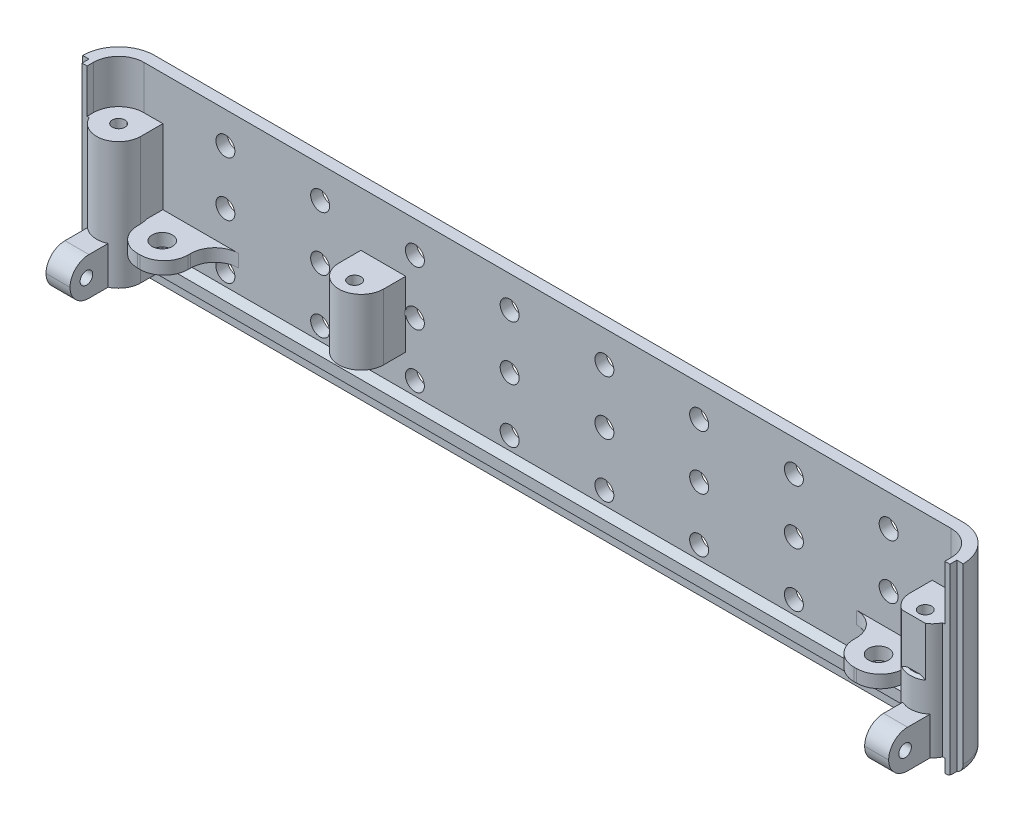
SolidWorks part; units mm, degrees
ref_plane "Спереди" through (0, 0, 0) normal (0, 0, 1) x (1, 0, 0)
ref_plane "Сверху" through (0, 0, 0) normal (0, 1, 0) x (1, 0, 0)
ref_plane "Справа" through (0, 0, 0) normal (1, 0, 0) x (0, 0, -1)
sketch "Эскиз1" plane through (0, 0, 0) normal (0, 0, 1) x (1, 0, 0)
  line L0 (63.5, -15.75) -> (-63.5, -15.75)
  line L1 (63.5, -15.75) -> (67.5, -15.75)
  line L2 (-67.5, -15.75) -> (-63.5, -15.75)
  line L3 (46.9932, -6.75) -> (37.9073, -6.75)
  line L4 (37.9073, -5.75) -> (46.9932, -5.75)
  line L5 (47.9512, -6.625) -> (47.9512, -6.1632)
  line L6 (47.912, -5.875) -> (47.023, -5.875)
  line L7 (47.023, -5.875) -> (47.023, -6.625)
  line L8 (47.023, -6.625) -> (47.9512, -6.625)
  line L9 (36.95, -6.1597) -> (36.95, -6.625)
  line L10 (36.95, -6.625) -> (37.8781, -6.625)
  line L11 (37.8781, -6.625) -> (37.8781, -5.875)
  line L12 (37.8781, -5.875) -> (36.9862, -5.875)
  line L13 (67.5, -13.75) -> (67.5, -15.75)
  line L14 (-67.5, -13.75) -> (-67.5, -15.75)
  line L15 (63.5, -13.75) -> (-63.5, -13.75)
  line L16 (57.5, -7.55) -> (-57.5, -7.55)
  line L17 (-60, -7.55) -> (-60, -9.15)
  line L18 (60, -9.15) -> (60, -7.55)
  line L19 (37.2238, 0.43) -> (27.8238, 0.43)
  line L20 (37.2238, -0.52) -> (27.8238, -0.52)
  line L21 (27.0238, -0.52) -> (27.0238, 0.43)
  line L22 (38.0238, 0.43) -> (38.0238, -0.52)
  line L23 (38.325, 15.75) -> (32.995, 15.75)
  line L24 (43.655, 15.75) -> (38.325, 15.75)
  line L25 (67.5, -13.75) -> (63.5, -13.75)
  line L26 (-63.5, -13.75) -> (-67.5, -13.75)
  line L27 (-26.445, 5.4154) -> (64.8363, 5.4154)
  line L28 (-26.445, 7.0154) -> (64.8363, 7.0154)
  line L29 (63.0185, 5.4154) -> (66.0185, 5.4154)
  line L30 (-24.6275, 7.05) -> (-27.6275, 7.05)
  arc A0 (-11.5687, 1.25) -> (-15.0687, 1.25) centre (-13.3187, 1.25) ccw
  arc A1 (-15.0687, 1.25) -> (-11.5687, 1.25) centre (-13.3187, 1.25) ccw
  arc A2 (53.36, 1.25) -> (49.86, 1.25) centre (51.61, 1.25) ccw
  arc A3 (49.86, 1.25) -> (53.36, 1.25) centre (51.61, 1.25) ccw
  arc A4 (17.6413, 1.25) -> (14.1413, 1.25) centre (15.8913, 1.25) ccw
  arc A5 (14.1413, 1.25) -> (17.6413, 1.25) centre (15.8913, 1.25) ccw
  arc A6 (-1.428, -0.6365) -> (-1.4312, -5.6346) centre (0.0417, -3.1365) ccw
  arc A7 (1.5146, -5.6346) -> (1.5114, -0.6365) centre (0.0417, -3.1365) ccw
  spline S0 degree 3 poles (47.9512, -6.1632) (47.951, -6.1513) (47.9493, -6.1307) (47.9471, -6.1018) knots 0 0 0 0 0.000128 0.000128 0.000128 0.000128 weights 1 1 1 1
  spline S1 degree 3 poles (47.9471, -6.1018) (47.9414, -6.0263) (47.9296, -5.9508) (47.912, -5.875) knots 0 0 0 0 0.000334 0.000334 0.000334 0.000334 weights 1 1 1 1
  spline S2 degree 3 poles (36.953, -6.1018) (36.9512, -6.1281) (36.95, -6.1474) (36.95, -6.1597) knots 0 0 0 0 0.000115 0.000115 0.000115 0.000115 weights 1 1 1 1
  spline S3 degree 3 poles (36.9862, -5.875) (36.9691, -5.9508) (36.958, -6.0264) (36.953, -6.1018) knots 0 0 0 0 0.000335 0.000335 0.000335 0.000335 weights 1 1 1 1
sketch "Эскиз2" plane through (0, 0, 0) normal (0, 0, 1) x (1, 0, 0)
  line L0 (43.655, 15.75) -> (38.325, 15.75) construction
  line L1 (-69.7, 13.75) -> (69.7, 13.75)
  line L2 (-69.7, 13.75) -> (-69.7, -15.35)
  line L3 (-69.7, -15.35) -> (69.7, -15.35)
  line L4 (69.7, 13.75) -> (69.7, -15.35)
  line L5 (63.5, -15.75) -> (-63.5, -15.75) construction
  line L6 (67.5, -13.75) -> (67.5, -15.75) construction
  line L7 (-67.5, -13.75) -> (-67.5, -15.75) construction
  dimension "D1" = 2
  dimension "D2" = 0.4
  dimension "D3" = 2.2
  dimension "D4" = 2.2
extrude "Бобышка-Вытянуть1" add sketch "Эскиз2" along normal blind 1.8
sketch "Эскиз5" plane through (0, 0, 0) normal (0, 0, -1) x (-1, 0, 0)
  line L0 (69.7, -15.35) -> (-69.7, -15.35) construction
  line L1 (69.7, 13.75) -> (67.9, 13.75)
  line L2 (69.7, 13.75) -> (69.7, -15.35)
  line L3 (69.7, -15.35) -> (67.9, -15.35)
  line L4 (67.9, 13.75) -> (67.9, -15.35)
  line L5 (-63.5, -15.75) -> (63.5, -15.75) construction
  line L6 (-69.7, 13.75) -> (-67.9, 13.75)
  line L7 (-69.7, 13.75) -> (-69.7, -15.75)
  line L8 (-69.7, -15.75) -> (-67.9, -15.75)
  line L9 (-67.9, 13.75) -> (-67.9, -15.75)
  dimension "D1" = 1.8
  dimension "D2" = 1.8
extrude "Бобышка-Вытянуть2" add sketch "Эскиз5" along normal blind 5
fillet "Скругление1" radius 4 2 edges at (-67.9, -0.8, 0) (67.9, -0.8, 0)
fillet "Скругление2" radius 5.7 2 edges at (69.7, -0.8, 1.8) (-69.7, -0.8, 1.8)
sketch "Эскиз12" plane through (67.9, 0, 0) normal (-1, 0, 0) x (0, 0, 1)
  line L1 (-5, -15.75) -> (0, -15.75)
  line L2 (-5, -15.75) -> (-5, -15.35)
  line L3 (-5, -15.35) -> (0, -15.35)
  line L4 (0, -15.75) -> (0, -15.35)
extrude "Вырез-Вытянуть6" cut sketch "Эскиз12" against normal blind 11.4
sketch "Эскиз13" plane through (0, 0, 0) normal (0, 0, -1) x (-1, 0, 0)
  line L0 (-57.5, -7.55) -> (57.5, -7.55) construction
  line L1 (-60.7, -4.95) -> (-52.7, -4.95)
  line L2 (-60.7, -4.95) -> (-60.7, -6.95)
  line L3 (-60.7, -6.95) -> (-52.7, -6.95)
  line L4 (-52.7, -4.95) -> (-52.7, -6.95)
  line L5 (-60, -9.15) -> (-60, -7.55) construction
  line L6 (60, -7.55) -> (60, -9.15) construction
  line L7 (52.7, -4.95) -> (60.7, -4.95)
  line L8 (52.7, -4.95) -> (52.7, -6.95)
  line L9 (52.7, -6.95) -> (60.7, -6.95)
  line L10 (60.7, -4.95) -> (60.7, -6.95)
  dimension "D1" = 8
  dimension "D2" = 2
  dimension "D3" = 0.6
  dimension "D4" = 0.7
  dimension "D5" = 8
  dimension "D6" = 2
  dimension "D7" = 0.6
  dimension "D8" = 0.7
extrude "Бобышка-Вытянуть3" add sketch "Эскиз13" along normal blind 8
sketch "Эскиз14" plane through (0, -4.95, 0) normal (0, 1, 0) x (1, 0, 0)
  line L0 (60.7, 8) -> (60.7, 0) construction
  line L1 (52.7, 8) -> (60.7, 8) construction
  line L2 (-60.7, 8) -> (-60.7, 0) construction
  line L3 (-60.7, 8) -> (-52.7, 8) construction
  circle A0 centre (-56.7, 4.3) radius 1.6
  circle A1 centre (56.7, 4.3) radius 1.6
  dimension "D1" = 3.2
  dimension "D2" = 4
  dimension "D3" = 3.7
  dimension "D4" = 4
  dimension "D5" = 3.7
extrude "Вырез-Вытянуть7" cut sketch "Эскиз14" against normal blind 10
fillet "Скругление3" radius 3.8 8 edges at (60.7, -5.95, -8) (52.7, -5.95, -8) (-60.7, -5.95, 0) (52.7, -5.95, 0) (60.7, -5.95, 0) (-52.7, -5.95, 0) (-60.7, -5.95, -8) (-52.7, -5.95, -8)
sketch "Эскиз18" plane through (0, -15.35, 0) normal (0, -1, 0) x (1, 0, 0)
  line L0 (67.9, -4) -> (67.9, -5) construction
  line L1 (67.9, -4) -> (67.9, -5)
  line L2 (-63.9, 0) -> (63.9, 0) construction
  line L3 (-63.9, 0) -> (63.9, 0)
  line L4 (-67.9, -5) -> (-67.9, -4) construction
  line L5 (-67.9, -5) -> (-67.9, -4)
  arc A0 (67.9, -4) -> (63.9, 0) centre (63.9, -4) ccw construction
  arc A1 (67.9, -4) -> (63.9, 0) centre (63.9, -4) ccw
  arc A2 (-63.9, 0) -> (-67.9, -4) centre (-63.9, -4) ccw construction
  arc A3 (-63.9, 0) -> (-67.9, -4) centre (-63.9, -4) ccw
extrude "Вытянуть-Тонкостенный1" add sketch "Эскиз18" against normal blind 3.8 and the other way blind 1 thin thin type one direction wall 1
sketch "Эскиз19" plane through (0, -16.35, 0) normal (0, -1, 0) x (1, 0, 0)
  line L8 (66.9, -4) -> (66.9, -5)
  line L9 (66.9, -5) -> (67.9, -5)
  line L10 (67.9, -5) -> (67.9, -4)
  line L11 (63.9, 0) -> (-63.9, 0)
  line L12 (-67.9, -4) -> (-67.9, -5)
  line L13 (-67.9, -5) -> (-66.9, -5)
  line L14 (-66.9, -5) -> (-66.9, -4)
  line L15 (-63.9, -1) -> (63.9, -1)
  line L16 (66.9, -4) -> (66.9, -5)
  line L17 (66.9, -5) -> (67.9, -5)
  line L18 (67.9, -5) -> (67.9, -4)
  line L19 (63.9, 0) -> (-63.9, 0)
  line L20 (-67.9, -4) -> (-67.9, -5)
  line L21 (-67.9, -5) -> (-66.9, -5)
  line L22 (-66.9, -5) -> (-66.9, -4)
  line L23 (-63.9, -1) -> (63.9, -1)
  arc A4 (67.9, -4) -> (63.9, 0) centre (63.9, -4) ccw
  arc A5 (-63.9, 0) -> (-67.9, -4) centre (-63.9, -4) ccw
  arc A6 (-63.9, -1) -> (-66.9, -4) centre (-63.9, -4) ccw
  arc A7 (66.9, -4) -> (63.9, -1) centre (63.9, -4) ccw
  arc A8 (67.9, -4) -> (63.9, 0) centre (63.9, -4) ccw
  arc A9 (-63.9, 0) -> (-67.9, -4) centre (-63.9, -4) ccw
  arc A10 (-63.9, -1) -> (-66.9, -4) centre (-63.9, -4) ccw
  arc A11 (66.9, -4) -> (63.9, -1) centre (63.9, -4) ccw
  dimension "D1" = 0
extrude "Вырез-Вытянуть8" cut sketch "Эскиз19" against normal blind 3.1
sketch "Эскиз20" plane through (0, -11.55, 0) normal (0, 1, 0) x (1, 0, 0)
  line L0 (67.9, 5) -> (67.9, 4) construction
  line L1 (-63.9, 0) -> (63.9, 0) construction
  line L2 (-67.9, 5) -> (-67.9, 4) construction
  circle A0 centre (-64.4, 3.5) radius 3.5
  circle A1 centre (64.4, 3.5) radius 3.5
  circle A2 centre (-26, 3.5) radius 3.55
  dimension "D1" = 7
  dimension "D2" = 7
  dimension "D3" = 3.5
  dimension "D4" = 3.5
  dimension "D5" = 3.5
  dimension "D6" = 3.5
  dimension "D7" = 7.1
  dimension "D8" = 90.4
extrude "Бобышка-Вытянуть6" add sketch "Эскиз20" along normal blind 16.7 and the other way blind 1.7
sketch "Эскиз23" plane through (0, 5.15, 0) normal (0, 1, 0) x (1, 0, 0)
  circle A0 centre (-64.4, 3.5) radius 1
  circle A1 centre (-26, 3.5) radius 1
  circle A2 centre (64.4, 3.5) radius 1
  dimension "D1" = 2
extrude "Вырез-Вытянуть9" cut sketch "Эскиз23" against normal blind 20
sketch "Эскиз24" plane through (0, 5.15, 0) normal (0, 1, 0) x (1, 0, 0)
  line L2 (-67.9, 5) -> (-67.2764, 5)
  line L3 (-67.9, 5) -> (-67.9, 2.059)
  line L4 (-67.9, 2.059) -> (-67.2764, 2.059)
  line L5 (-67.2764, 5) -> (-67.2764, 2.059)
  line L6 (-60.9, 3.5) -> (-62.4575, 3.5)
  line L7 (-60.9, 3.5) -> (-60.9, -0.9822)
  line L8 (-60.9, -0.9822) -> (-62.4575, -0.9822)
  line L9 (-62.4575, 3.5) -> (-62.4575, -0.9822)
  line L10 (-64.1584, 0.0084) -> (-62.4575, 0.0084)
  line L11 (-64.1584, 0.0084) -> (-64.1584, 2.059)
  line L12 (-64.1584, 2.059) -> (-62.4575, 2.059)
  line L13 (-62.4575, 0.0084) -> (-62.4575, 2.059)
  line L14 (-29.55, 3.5) -> (-28.2836, 3.5)
  line L15 (-29.55, 3.5) -> (-29.55, -0.9822)
  line L16 (-29.55, -0.9822) -> (-28.2836, -0.9822)
  line L17 (-28.2836, 3.5) -> (-28.2836, -0.9822)
  line L18 (-22.45, 3.5) -> (-24.2804, 3.5)
  line L19 (-22.45, 3.5) -> (-22.45, -0.9822)
  line L20 (-22.45, -0.9822) -> (-24.2804, -0.9822)
  line L21 (-24.2804, 3.5) -> (-24.2804, -0.9822)
  line L22 (67.8916, 3.7416) -> (66.8457, 3.7416)
  line L23 (67.8916, 3.7416) -> (67.8916, 5)
  line L24 (67.8916, 5) -> (66.8457, 5)
  line L25 (66.8457, 3.7416) -> (66.8457, 5)
  line L26 (60.9, 3.5) -> (62.7277, 3.5)
  line L27 (60.9, 3.5) -> (60.9, -0.9822)
  line L28 (60.9, -0.9822) -> (62.7277, -0.9822)
  line L29 (62.7277, 3.5) -> (62.7277, -0.9822)
  line L30 (64.1584, 0.0084) -> (62.7277, 0.0084)
  line L31 (64.1584, 0.0084) -> (64.1584, 1.4963)
  line L32 (64.1584, 1.4963) -> (62.7277, 1.4963)
  line L33 (62.7277, 0.0084) -> (62.7277, 1.4963)
  line L34 (-28.2836, 1.2589) -> (-24.2804, 1.2589)
  line L35 (-28.2836, 1.2589) -> (-28.2836, -0.9822)
  line L36 (-28.2836, -0.9822) -> (-24.2804, -0.9822)
  line L37 (-24.2804, 1.2589) -> (-24.2804, -0.9822)
  arc A0 (-64.1584, 0.0084) -> (-67.8916, 3.7416) centre (-64.4, 3.5) ccw construction
  arc A1 (-25.4063, 0) -> (-26.5937, 0) centre (-26, 3.5) ccw construction
  arc A2 (67.8916, 3.7416) -> (64.1584, 0.0084) centre (64.4, 3.5) ccw construction
  arc M2 (-67.8916, 3.7416) -> (-64.1584, 0.0084) centre (-63.9, 4) ccw
  arc M3 (-64.1584, 0.0084) -> (-67.8916, 3.7416) centre (-64.4, 3.5) ccw
extrude "Бобышка-Вытянуть9" add sketch "Эскиз24" against normal blind 18.4 contours L25 L22 L23 L24 | L31 L32 L29 L30 | L29 L26 L27 L28 | L18 L21 L20 L19 | L17 L14 L15 L16 | L9 L8 L7 M3 | L12 L11 L9 M3 | L5 L2 L4 M3 M2 | L3 L2 L5 L4 | L11 L10 L13 L12 | L35 L34 L37 L36 region at (-67.5246, 5.15, -3.6272) region at (-61.5592, 5.15, -0.3271) region at (-63.3519, 5.15, -1.1295) region at (-28.9168, 5.15, -1.2589) region at (-23.3652, 5.15, -1.2589) region at (67.3687, 5.15, -4.3708) region at (61.8139, 5.15, -1.2589) region at (63.443, 5.15, -0.7523)
sketch "Эскиз25" plane through (0, 5.15, 0) normal (0, 1, 0) x (1, 0, 0)
  line L6 (-64.1584, 0.0084) -> (-62.4575, 0.0084)
  line L7 (-62.4575, 0.0084) -> (-62.4575, 0)
  line L8 (-62.4575, 0) -> (-60.9, 0)
  line L9 (-60.9, 0) -> (-60.9, 3.5)
  line L10 (-67.5623, 5) -> (-67.9, 5)
  line L11 (-67.9, 5) -> (-67.9, 4)
  line L12 (-64.1584, 0.0084) -> (-62.4575, 0.0084)
  line L13 (-62.4575, 0.0084) -> (-62.4575, 0)
  line L14 (-62.4575, 0) -> (-60.9, 0)
  line L15 (-60.9, 0) -> (-60.9, 3.5)
  line L16 (-67.5623, 5) -> (-67.9, 5)
  line L17 (-67.9, 5) -> (-67.9, 4)
  circle A0 centre (-64.4, 3.5) radius 1 construction
  circle A1 centre (-64.4, 3.5) radius 1
  arc A2 (-67.9, 4) -> (-64.1584, 0.0084) centre (-63.9, 4) ccw
  arc A3 (-60.9, 3.5) -> (-67.5623, 5) centre (-64.4, 3.5) ccw
  arc A4 (-67.9, 4) -> (-64.1584, 0.0084) centre (-63.9, 4) ccw
  arc A5 (-60.9, 3.5) -> (-67.5623, 5) centre (-64.4, 3.5) ccw
  dimension "D1" = 0
extrude "Бобышка-Вытянуть10" add sketch "Эскиз25" along normal blind 1.7
sketch "Эскиз26" plane through (0, -13.25, 0) normal (0, -1, 0) x (1, 0, 0)
  line L1 (-63.9, 0) -> (63.9, 0) construction
  line L2 (-29.55, 0) -> (-22.45, 0)
  line L3 (-29.55, 0) -> (-29.55, -7.05)
  line L4 (-29.55, -7.05) -> (-22.45, -7.05)
  line L5 (-22.45, 0) -> (-22.45, -7.05)
extrude "Вырез-Вытянуть10" cut sketch "Эскиз26" against normal blind 8
sketch "Эскиз27" plane through (-29.55, 0, 0) normal (1, 0, 0) x (0, 0, -1)
  line L4 (1, -11.55) -> (0, -11.55)
  line L5 (0, -11.55) -> (0, -13.25)
  line L6 (0, -13.25) -> (1, -13.25)
  line L7 (1, -13.25) -> (1, -11.55)
  line L8 (1, -11.55) -> (0, -11.55)
  line L9 (0, -11.55) -> (0, -13.25)
  line L10 (0, -13.25) -> (1, -13.25)
  line L11 (1, -13.25) -> (1, -11.55)
  dimension "D1" = 0
extrude "Бобышка-Вытянуть11" add sketch "Эскиз27" along normal blind 8
sketch "Эскиз29" plane through (69.7, 0, 0) normal (1, 0, 0) x (0, 0, -1)
  line L1 (7.05, 5.15) -> (6.45, 5.15)
  line L2 (7.05, 5.15) -> (7.05, -1.25)
  line L3 (7.05, -1.25) -> (6.45, -1.25)
  line L4 (6.45, 5.15) -> (6.45, -1.25)
  dimension "D1" = 6.4
  dimension "D2" = 0.6
extrude "Вырез-Вытянуть11" cut sketch "Эскиз29" against normal blind 8
sketch "Эскиз30" plane through (69.7, 0, 0) normal (1, 0, 0) x (0, 0, -1)
  line L4 (3.9, 13.75) -> (3.9, -15.35)
  line L5 (3.9, -15.35) -> (5, -15.35)
  line L6 (5, -15.35) -> (5, 13.75)
  line L7 (5, 13.75) -> (3.9, 13.75)
  line L8 (3.9, 13.75) -> (3.9, -15.35)
  line L9 (3.9, -15.35) -> (5, -15.35)
  line L10 (5, -15.35) -> (5, 13.75)
  line L11 (5, 13.75) -> (3.9, 13.75)
  dimension "D1" = 0
extrude "Вырез-Вытянуть12" cut sketch "Эскиз30" against normal blind 1
mirror "Зеркальное отражение9" about plane through (0, 0, 1.8) normal (0, 0, 1) of "Бобышка-Вытянуть2", "Скругление2", "Вырез-Вытянуть7", "Скругление3", "Вырез-Вытянуть8", "Бобышка-Вытянуть6", "Вырез-Вытянуть9", "Бобышка-Вытянуть10", "Вырез-Вытянуть10", "Вырез-Вытянуть11", "Вырез-Вытянуть12", "Скругление1", "Бобышка-Вытянуть3", "Бобышка-Вытянуть1", "Вытянуть-Тонкостенный1", "Бобышка-Вытянуть9"
sketch "Эскиз31" plane through (0, 13.75, 0) normal (0, 1, 0) x (1, 0, 0)
  line L1 (-71.3653, -1.8) -> (75.7829, -1.8)
  line L2 (-71.3653, -1.8) -> (-71.3653, 18.9346)
  line L3 (-71.3653, 18.9346) -> (75.7829, 18.9346)
  line L4 (75.7829, -1.8) -> (75.7829, 18.9346)
extrude "Вырез-Вытянуть13" cut sketch "Эскиз31" against normal blind 40
sketch "Эскиз33" plane through (67.9, 0, 0) normal (-1, 0, 0) x (0, 0, 1)
  line L1 (3.6, -15.35) -> (8.6, -15.35)
  line L2 (3.6, -15.35) -> (3.6, -15.75)
  line L3 (3.6, -15.75) -> (8.6, -15.75)
  line L4 (8.6, -15.35) -> (8.6, -15.75)
extrude "Вырез-Вытянуть14" cut sketch "Эскиз33" against normal blind 10
sketch "Эскиз34" plane through (-22.45, 0, 0) normal (-1, 0, 0) x (0, 0, 1)
  line L4 (4.6, -11.55) -> (3.6, -11.55)
  line L5 (3.6, -11.55) -> (3.6, -13.25)
  line L6 (3.6, -13.25) -> (4.6, -13.25)
  line L7 (4.6, -13.25) -> (4.6, -11.55)
  line L8 (4.6, -11.55) -> (3.6, -11.55)
  line L9 (3.6, -11.55) -> (3.6, -13.25)
  line L10 (3.6, -13.25) -> (4.6, -13.25)
  line L11 (4.6, -13.25) -> (4.6, -11.55)
  dimension "D1" = 0
extrude "Бобышка-Вытянуть12" add sketch "Эскиз34" along normal blind 10
sketch "Эскиз35" plane through (-69.7, 0, 0) normal (-1, 0, 0) x (0, 0, 1)
  line L4 (8.6, 13.75) -> (7.5, 13.75)
  line L5 (7.5, 13.75) -> (7.5, -15.35)
  line L6 (7.5, -15.35) -> (8.6, -15.35)
  line L7 (8.6, -15.35) -> (8.6, 13.75)
  line L8 (8.6, 13.75) -> (7.5, 13.75)
  line L9 (7.5, 13.75) -> (7.5, -15.35)
  line L10 (7.5, -15.35) -> (8.6, -15.35)
  line L11 (8.6, -15.35) -> (8.6, 13.75)
  dimension "D1" = 0
extrude "Вырез-Вытянуть15" cut sketch "Эскиз35" against normal blind 1
sketch "Эскиз36" plane through (0, -1.25, 0) normal (0, 1, 0) x (1, 0, 0)
  line L1 (66.2835, -10.05) -> (62.5165, -10.05)
  line L2 (66.2835, -10.05) -> (62.5165, -10.05)
  arc A1 (62.5165, -10.05) -> (66.2835, -10.05) centre (64.4, -7.1) ccw
  arc A2 (62.5165, -10.05) -> (66.2835, -10.05) centre (64.4, -7.1) ccw
  dimension "D1" = 0
extrude "Вырез-Вытянуть16" cut sketch "Эскиз36" against normal blind 1
chamfer "Фаска1" distance 0.4 angle 45 1 edges at (64.4, -2.25, 10.6)
chamfer "Фаска2" distance 1 angle 45 1 edges at (0, -11.55, 3.6)
sketch "Эскиз37" plane through (0, 0, 1.8) normal (0, 0, -1) x (-1, 0, 0)
  line L12 (64, 13.75) -> (-64, 13.75) construction
  line L13 (-62, 13.75) -> (-59, 13.75)
  line L14 (-62, 13.75) -> (-62, -13.35)
  line L15 (-62, -13.35) -> (-59, -13.35)
  line L16 (-59, 13.75) -> (-59, -13.35)
  line L17 (-64, -15.35) -> (-64, 13.75) construction
  line L18 (59, 13.75) -> (62, 13.75)
  line L19 (59, 13.75) -> (59, -13.35)
  line L20 (59, -13.35) -> (62, -13.35)
  line L21 (62, 13.75) -> (62, -13.35)
  line L22 (64, 13.75) -> (64, -15.35) construction
  line L23 (64, -15.35) -> (-64, -15.35) construction
  dimension "D1" = 3
  dimension "D2" = 2
  dimension "D3" = 2
  dimension "D4" = 3
  dimension "D5" = 2
  dimension "D6" = 2
extrude "Бобышка-Вытянуть13" add sketch "Эскиз37" along normal blind 2
sketch "Эскиз38" plane through (0, 0, 1.8) normal (0, 0, -1) x (-1, 0, 0)
  line L2 (59, 13.75) -> (-59, 13.75) construction
  line L3 (-59, -13.35) -> (-59, 13.75) construction
  circle A0 centre (-54, 8.75) radius 1.5
  circle A1 centre (-39, 8.75) radius 1.5
  circle A2 centre (-24, 8.75) radius 1.5
  circle A3 centre (-9, 8.75) radius 1.5
  circle A4 centre (6, 8.75) radius 1.5
  circle A5 centre (21, 8.75) radius 1.5
  circle A6 centre (36, 8.75) radius 1.5
  circle A7 centre (51, 8.75) radius 1.5
  circle A8 centre (-39, 0.15) radius 1.5
  circle A9 centre (-24, 0.15) radius 1.5
  circle A10 centre (-9, 0.15) radius 1.5
  circle A11 centre (6, 0.15) radius 1.5
  circle A12 centre (21, 0.15) radius 1.5
  circle A13 centre (36, 0.15) radius 1.5
  circle A14 centre (51, 0.15) radius 1.5
  circle A15 centre (-39, -8.45) radius 1.5
  circle A16 centre (-24, -8.45) radius 1.5
  circle A17 centre (-9, -8.45) radius 1.5
  circle A18 centre (6, -8.45) radius 1.5
  circle A19 centre (21, -8.45) radius 1.5
  circle A20 centre (36, -8.45) radius 1.5
  circle A21 centre (51, -8.45) radius 1.5
  circle A22 centre (-54, 0.15) radius 1.5
  circle A23 centre (-54, -8.45) radius 1.5
  dimension "D1" = 3
  dimension "D2" = 5
  dimension "D3" = 5
  dimension "D4" = 8
  dimension "D5" = 3
extrude "Вырез-Вытянуть17" cut sketch "Эскиз38" against normal blind 2
sketch "Эскиз39" plane through (0, 5.15, 0) normal (0, 1, 0) x (1, 0, 0)
  circle A0 centre (-26, -7.1) radius 1 construction
  circle A1 centre (-26, -7.1) radius 1
  circle A2 centre (64.4, -7.1) radius 1 construction
  circle A3 centre (64.4, -7.1) radius 1
extrude "Бобышка-Вытянуть14" add sketch "Эскиз39" against normal blind 10.4
sketch "Эскиз40" plane through (0, 5.15, 0) normal (0, 1, 0) x (1, 0, 0)
  line L0 (-22.45, -7.1) -> (-22.45, -3.6) construction
  line L1 (60.9, -7.1) -> (60.9, -3.6) construction
  line L2 (63.9, -3.6) -> (-63.9, -3.6) construction
  circle A0 centre (-25.95, -8.2) radius 1
  circle A1 centre (64.4, -8.2) radius 1
  dimension "D1" = 2
  dimension "D2" = 2
  dimension "D3" = 3.5
  dimension "D5" = 4.6
  dimension "D6" = 4.6
  dimension "D4" = 3.5
extrude "Вырез-Вытянуть18" cut sketch "Эскиз40" against normal blind 10.4
sketch "Эскиз41" plane through (0, 0, 8.6) normal (0, 0, 1) x (1, 0, 0)
  line L0 (68.7, 13.75) -> (68.7, -15.35) construction
  line L1 (68.7, 13.75) -> (68.7, -15.35)
  line L2 (68.7, -15.35) -> (67.9, -15.35) construction
  line L3 (68.7, -15.35) -> (67.9, -15.35)
  line L4 (67.9, -13.25) -> (67.9, -15.35) construction
  line L5 (67.9, -13.25) -> (67.9, -15.35)
  line L6 (67.5623, -13.25) -> (67.9, -13.25) construction
  line L7 (67.5623, -13.25) -> (67.9, -13.25)
  line L8 (67.5623, 5.15) -> (67.5623, -13.25) construction
  line L9 (67.5623, 5.15) -> (67.5623, -13.25)
  line L10 (67.8916, 5.15) -> (67.5623, 5.15) construction
  line L11 (67.8916, 5.15) -> (67.5623, 5.15)
  line L12 (67.9, 13.75) -> (68.7, 13.75) construction
  line L13 (67.9, 13.75) -> (68.7, 13.75)
  line L14 (67.9, 13.75) -> (67.9, 5.15)
  line L15 (67.9, -11.55) -> (67.9, 13.75) construction
  line L16 (67.9, 5.15) -> (67.8916, 5.15)
extrude "Бобышка-Вытянуть15" add sketch "Эскиз41" against normal blind 0.8
sketch "Эскиз42" plane through (-67.9, 0, 0) normal (1, 0, 0) x (0, 0, -1)
  line L1 (-8.6, -13.25) -> (-16.3, -13.25)
  line L2 (-8.6, -13.25) -> (-8.6, -7.25)
  line L3 (-8.6, -7.25) -> (-16.3, -7.25)
  line L4 (-16.3, -13.25) -> (-16.3, -7.25)
  dimension "D1" = 7.7
  dimension "D2" = 6
extrude "Бобышка-Вытянуть16" add sketch "Эскиз42" along normal blind 5
sketch "Эскиз43" plane through (67.9, 0, 0) normal (-1, 0, 0) x (0, 0, 1)
  line L1 (8.6, -13.25) -> (16.3, -13.25)
  line L2 (8.6, -13.25) -> (8.6, -7.25)
  line L3 (8.6, -7.25) -> (16.3, -7.25)
  line L4 (16.3, -13.25) -> (16.3, -7.25)
  dimension "D1" = 7.7
  dimension "D2" = 6
extrude "Бобышка-Вытянуть17" add sketch "Эскиз43" along normal blind 5
sketch "Эскиз44" plane through (0, -7.25, 0) normal (0, 1, 0) x (1, 0, 0)
  line L0 (67.9, -16.3) -> (67.9, -8.6) construction
  line L1 (67.9, -16.3) -> (67.9, -8.6)
  line L2 (67.5623, -8.6) -> (67.9, -8.6) construction
  line L3 (67.5623, -8.6) -> (67.9, -8.6)
  line L4 (67.9, -16.3) -> (66.7, -16.3)
  line L5 (62.9, -16.3) -> (67.9, -16.3) construction
  line L6 (66.7, -16.3) -> (66.7, -9.7382)
  line L7 (-67.5623, -8.6) -> (-67.9, -8.6) construction
  line L8 (-67.5623, -8.6) -> (-67.9, -8.6)
  line L9 (-67.9, -8.6) -> (-67.9, -16.3) construction
  line L10 (-67.9, -8.6) -> (-67.9, -16.3)
  line L11 (-67.9, -16.3) -> (-66.7, -16.3)
  line L12 (-62.9, -16.3) -> (-67.9, -16.3) construction
  line L13 (-66.7, -16.3) -> (-66.7, -9.7382)
  arc A0 (62.9, -10.2623) -> (67.5623, -8.6) centre (64.4, -7.1) ccw construction
  arc A1 (62.9, -10.2623) -> (67.5623, -8.6) centre (64.4, -7.1) ccw
  arc A2 (-67.5623, -8.6) -> (-62.9, -10.2623) centre (-64.4, -7.1) ccw construction
  arc A3 (-67.5623, -8.6) -> (-62.9, -10.2623) centre (-64.4, -7.1) ccw
  line M3 (67.9, -8.6) -> (67.5623, -8.6)
  arc M4 (67.5623, -8.6) -> (62.9, -10.2623) centre (64.4, -7.1) cw
  line M6 (62.9, -16.3) -> (67.9, -16.3)
  line M7 (67.9, -16.3) -> (67.9, -8.6)
  dimension "D1" = 1.2
  dimension "D2" = 1.2
extrude "Вырез-Вытянуть19" cut sketch "Эскиз44" against normal through all contours A3 L8 L10 L11 L13 | L6 M6 M7 M3 M4 region at (67.3188, -7.25, 12.6726) region at (-67.3188, -7.25, 12.6726)
fillet "Скругление4" radius 3 4 edges at (-64.8, -13.25, 16.3) (-64.8, -7.25, 16.3) (64.8, -13.25, 16.3) (64.8, -7.25, 16.3)
sketch "Эскиз45" plane through (66.7, 0, 0) normal (1, 0, 0) x (0, 0, -1)
  line L0 (-9.7382, -13.25) -> (-13.3, -13.25) construction
  circle A0 centre (-13.7, -10.25) radius 1
  dimension "D1" = 2
  dimension "D2" = 3
  dimension "D3" = 2.6
extrude "Вырез-Вытянуть20" cut sketch "Эскиз45" against normal through all
chamfer "Фаска5" distance 2 angle 45 4 edges at (-60.5, -13.35, -0.2) (-60.5, 13.75, -0.2) (60.5, 13.75, -0.2) (60.5, -13.35, -0.2)
fillet "Скругление6" radius 1.6 3 edges at (68.0305, -15.35, 3.4695) (-68.0305, -15.35, 3.4695) (0, -15.35, 1.8)
equation "\"52.8.00мм\"=5"
equation "\"0ю4\"=10"
